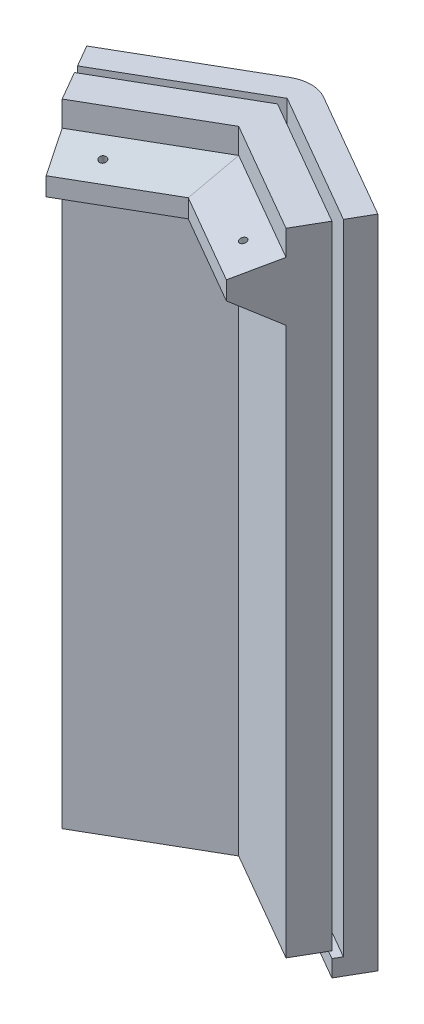
SolidWorks part; units mm, degrees
ref_plane "Front Plane" through (0, 0, 0) normal (0, 0, 1) x (1, 0, 0)
ref_plane "Top Plane" through (0, 0, 0) normal (0, 1, 0) x (1, 0, 0)
ref_plane "Right Plane" through (0, 0, 0) normal (1, 0, 0) x (0, 0, -1)
sketch "Sketch1" plane through (0, 0, 0) normal (0, 1, 0) x (1, 0, 0)
  line L0 (0, -153.0167) -> (0, 58.3538) construction
  line L1 (97.0301, 0) -> (-101.5537, 0) construction
  line L2 (-10, -5.7735) -> (-86.6025, -50)
  line L3 (10, -5.7735) -> (86.6025, -50)
  line L4 (0, -46.188) -> (66.6025, -84.641)
  line L5 (0, -46.188) -> (-66.6025, -84.641)
  line L6 (86.6025, -50) -> (66.6025, -84.641) construction
  line L7 (-86.6025, -50) -> (-66.6025, -84.641) construction
  line L8 (86.6025, -50) -> (79.1025, -62.9904)
  line L9 (79.1025, -62.9904) -> (53.1218, -47.9904)
  line L10 (53.1218, -47.9904) -> (50.6218, -52.3205)
  line L11 (50.6218, -52.3205) -> (76.6025, -67.3205)
  line L12 (76.6025, -67.3205) -> (66.6025, -84.641)
  line L13 (-86.6025, -50) -> (-79.1025, -62.9904)
  line L14 (-79.1025, -62.9904) -> (-53.1218, -47.9904)
  line L15 (-53.1218, -47.9904) -> (-50.6218, -52.3205)
  line L16 (-50.6218, -52.3205) -> (-76.6025, -67.3205)
  line L17 (-76.6025, -67.3205) -> (-66.6025, -84.641)
  circle A0 centre (0, -32) radius 20.5 construction
  arc A2 (-10, -5.7735) -> (10, -5.7735) centre (0, -23.094) cw
  point P24 (0, -46.188)
  point P27 (0, 0)
  dimension "D9" = 41
  dimension "D10" = 20
  dimension "D1" = 30
  dimension "D2" = 30
  dimension "D3" = 40
  dimension "D4" = 90
  dimension "D5" = 90
  dimension "D6" = 100
  dimension "D7" = 5
  dimension "D8" = 30
  dimension "D11" = 32
  dimension "D12" = 15
extrude "Boss-Extrude1" add sketch "Sketch1" along normal blind 390
sketch "Sketch18" plane through (0, 0, 0) normal (0, -1, 0) x (1, 0, 0)
  line L3 (-66.6025, 84.641) -> (0, 46.188) construction
  line L6 (-76.6025, 67.3205) -> (0, 23.094)
  line L7 (0, 23.094) -> (76.6025, 67.3205)
  line L8 (-76.6025, 67.3205) -> (0, 23.094)
  line L9 (0, 23.094) -> (76.6025, 67.3205)
  line L10 (0, 46.188) -> (66.6025, 84.641) construction
  line L11 (-66.6025, 84.641) -> (0, 46.188)
  line L12 (0, 46.188) -> (66.6025, 84.641)
  line L13 (76.6025, 67.3205) -> (66.6025, 84.641)
  line L15 (-76.6025, 67.3205) -> (-66.6025, 84.641)
  dimension "D1" = 20
extrude "Cut-Extrude2" cut sketch "Sketch18" against normal blind 14
sketch "Sketch19" plane through (0, 390, 0) normal (0, 1, 0) x (1, 0, 0)
  line L0 (76.6025, -67.3205) -> (50.6218, -52.3205) construction
  line L2 (76.6025, -67.3205) -> (0, -23.094)
  line L3 (79.1025, -62.9904) -> (76.6025, -67.3205)
  line L4 (53.1218, -47.9904) -> (79.1025, -62.9904) construction
  line L5 (0, -17.3205) -> (79.1025, -62.9904)
  line L6 (-79.1025, -62.9904) -> (-53.1218, -47.9904) construction
  line L7 (-79.1025, -62.9904) -> (0, -17.3205)
  line L8 (-50.6218, -52.3205) -> (-76.6025, -67.3205) construction
  line L9 (0, -23.094) -> (-76.6025, -67.3205)
  line L10 (-79.1025, -62.9904) -> (-76.6025, -67.3205)
extrude "Cut-Extrude3" cut sketch "Sketch19" against normal blind 50
sketch "Sketch20" plane through (0, 0, 0) normal (0, -1, 0) x (1, 0, 0)
  line L0 (76.6025, 67.3205) -> (50.6218, 52.3205) construction
  line L1 (53.1218, 47.9904) -> (79.1025, 62.9904) construction
  line L2 (50.6218, 52.3205) -> (53.1218, 47.9904) construction
  line L3 (-50.6218, 52.3205) -> (-76.6025, 67.3205) construction
  line L4 (-53.1218, 47.9904) -> (-50.6218, 52.3205) construction
  line L5 (-79.1025, 62.9904) -> (-53.1218, 47.9904) construction
  line L6 (76.6025, 67.3205) -> (50.6218, 52.3205)
  line L7 (53.1218, 47.9904) -> (79.1025, 62.9904)
  line L8 (50.6218, 52.3205) -> (53.1218, 47.9904)
  line L9 (-50.6218, 52.3205) -> (-76.6025, 67.3205)
  line L10 (-53.1218, 47.9904) -> (-50.6218, 52.3205)
  line L11 (-79.1025, 62.9904) -> (-53.1218, 47.9904)
  line L12 (79.1025, 62.9904) -> (76.6025, 67.3205)
  line L13 (-79.1025, 62.9904) -> (-76.6025, 67.3205)
extrude "Boss-Extrude2" add sketch "Sketch20" against normal blind 10
sketch "Sketch21" plane through (0, 0, 0) normal (1, 0, 0) x (0, 0, -1)
  line L0 (-46.188, 390) -> (-46.188, 14) construction
  line L1 (-46.188, 390) -> (-46.188, 14) construction
  line L2 (-46.188, 375) -> (-76.188, 368.2062)
  line L3 (-76.188, 368.2062) -> (-76.188, 357.3205)
  line L4 (-76.188, 357.3205) -> (-46.188, 340)
  line L5 (-46.188, 340) -> (-46.188, 375)
  line L6 (-46.188, 375) -> (-172.9071, 375) construction
  dimension "D1" = 361
  dimension "D2" = 12.76
  dimension "D3" = 30
  dimension "D4" = 60
  dimension "D5" = 35
extrude "Boss-Extrude3" add sketch "Sketch21" along direction (0.866, 0, -0.5) on the side against the normal up to surface (61.906 mm away) up to face at (-80.7692, 133.3333, 60.1036)
extrude "Boss-Extrude4" add sketch "Sketch21<2>" along direction (0.866, 0, 0.5) on the side of the normal up to surface (61.906 mm away) up to face at (71.6025, 202, 75.9808)
sketch "Sketch21<2>" plane through (0, 0, 0) normal (1, 0, 0) x (0, 0, -1) same geometry as "Sketch21"
sketch "Sketch22" plane through (47.1721, 360.7893, 81.7045) normal (0.1265, 0.9675, 0.2191) x (0.992, -0.1234, -0.0279)
  line L0 (-47.5541, 37.778) -> (-47.5541, 7.0184) construction
  line L1 (-101.6004, -23.1702) -> (-114.696, 0.2747) construction
  line L2 (-47.5541, 37.778) -> (-47.5541, 7.0184) construction
  line L3 (-101.6004, -23.1702) -> (-114.696, 0.2747) construction
  line L4 (-108.1482, -11.4478) -> (-56.0716, 17.6406) construction
  circle A0 centre (-89.6398, -1.1095) radius 2.1
  dimension "D1" = 4.2
  dimension "D2" = 21.2
extrude "Cut-Extrude4" cut sketch "Sketch22" against normal blind 15
mirror "Mirror1" about plane through (0, 0, 0) normal (1, 0, 0) of "Cut-Extrude4"
sketch "Sketch23" plane through (0, 14, 0) normal (0, -1, 0) x (1, 0, 0)
  line L0 (-66.6025, 84.641) -> (-76.6025, 67.3205) construction
  line L1 (-66.6025, 84.641) -> (-76.6025, 67.3205) construction
  line L2 (-71.6025, 75.9808) -> (0, 34.641) construction
  line L3 (0, 0) -> (0, 34.641) construction
  circle A0 centre (-25.9808, 49.641) radius 3.1
  circle A1 centre (-51.9615, 64.641) radius 3.1
  point P12 (-24.3353, 48.691)
  dimension "D1" = 6.2
  dimension "D2" = 30
  dimension "D3" = 30
extrude "Cut-Extrude5" cut sketch "Sketch23" against normal blind 60
mirror "Mirror2" about plane through (0, 0, 0) normal (1, 0, 0) of "Cut-Extrude5"
